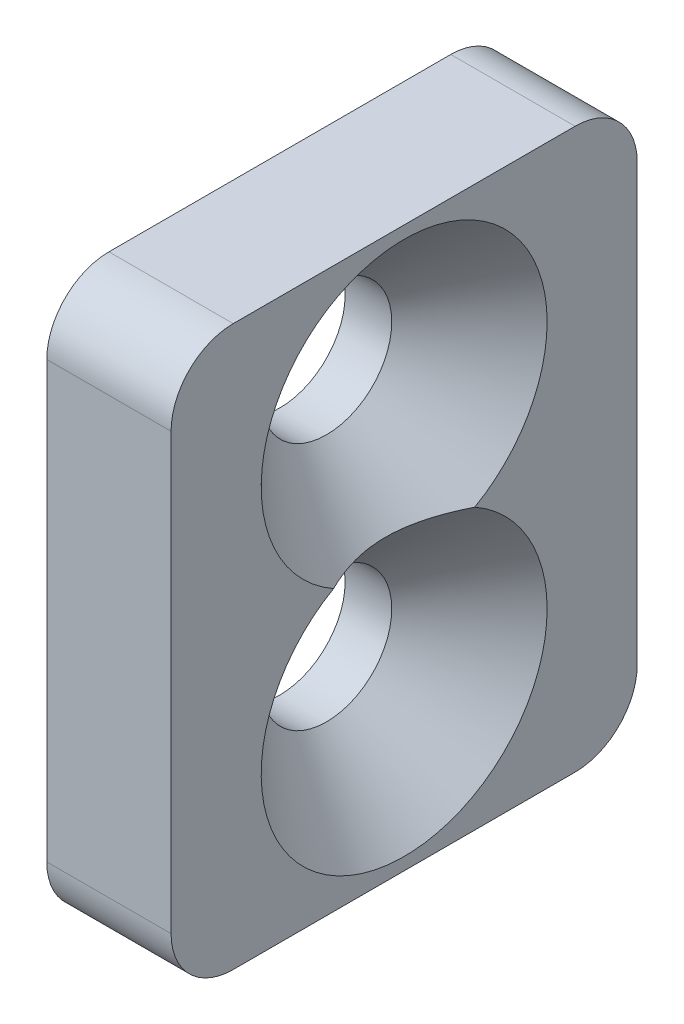
SolidWorks part; units mm, degrees
ref_plane "Front Plane" through (0, 0, 0) normal (0, 0, 1) x (1, 0, 0)
ref_plane "Top Plane" through (0, 0, 0) normal (0, 1, 0) x (1, 0, 0)
ref_plane "Right Plane" through (0, 0, 0) normal (1, 0, 0) x (0, 0, -1)
sketch "Sketch4" plane through (0, 0, 0) normal (1, 0, 0) x (0, 0, -1)
  line L0 (-7.5, 0) -> (7.5, 0) construction
  line L1 (-7.5, -9) -> (7.5, -9)
  line L2 (-7.5, -9) -> (-7.5, 9)
  line L3 (-7.5, 9) -> (7.5, 9)
  line L4 (7.5, -9) -> (7.5, 9)
  line L5 (-7.5, -9) -> (7.5, 9) construction
  line L6 (-7.5, 9) -> (7.5, -9) construction
  line L7 (0, 4) -> (0, -4) construction
  circle A0 centre (0, 4) radius 2.1
  circle A1 centre (0, -4) radius 2.1
  point P0 (0, 0)
  dimension "D3" = 8
  dimension "D4" = 4.2
  dimension "D1" = 18
  dimension "D2" = 15
extrude "Boss-Extrude1" add sketch "Sketch4" along normal blind 4
fillet "Fillet1" radius 2 4 edges at (2, -9, -7.5) (2, -9, 7.5) (2, 9, -7.5) (2, 9, 7.5)
chamfer "Chamfer1" distance 2.5 angle 45 2 edges at (4, -4, -2.1) (4, 4, -2.1)
